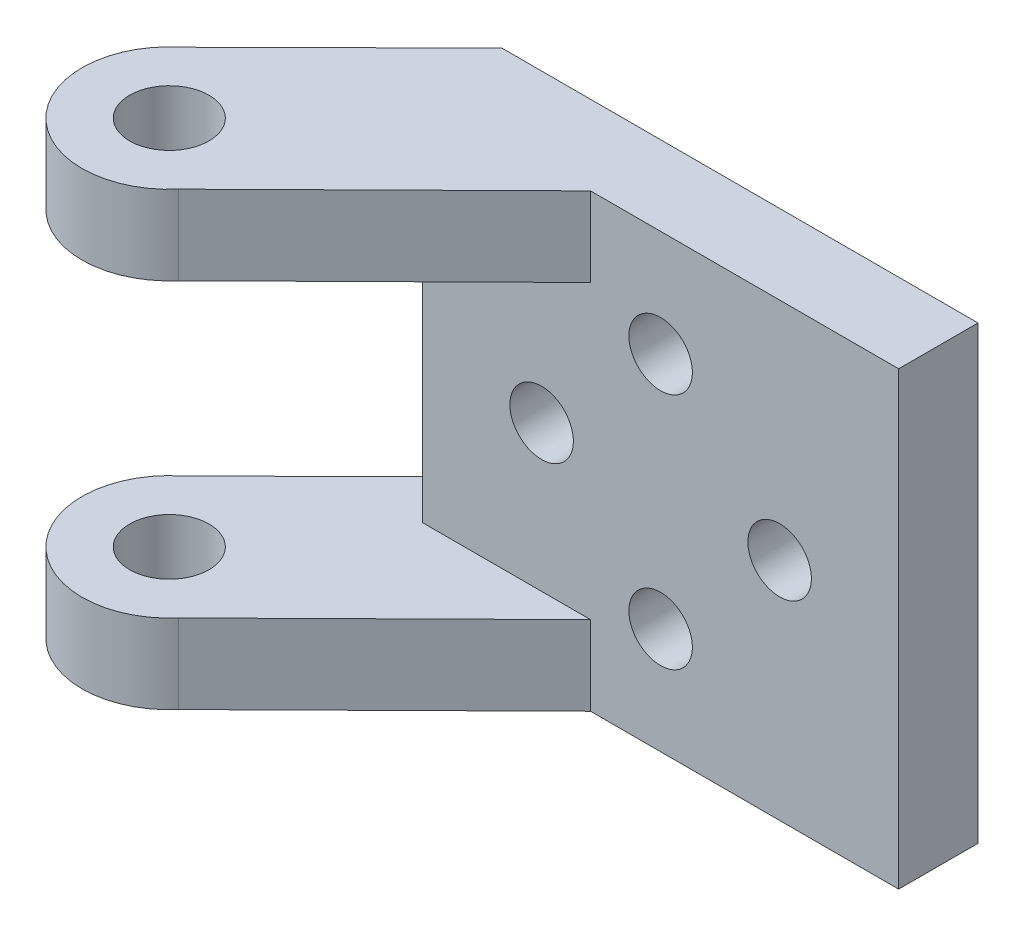
SolidWorks part; units mm, degrees
ref_plane "Front Plane" through (0, 0, 0) normal (0, 0, 1) x (1, 0, 0)
ref_plane "Top Plane" through (0, 0, 0) normal (0, 1, 0) x (1, 0, 0)
ref_plane "Right Plane" through (0, 0, 0) normal (1, 0, 0) x (0, 0, -1)
sketch "Sketch1" plane through (0, 0, 0) normal (0, 1, 0) x (1, 0, 0)
  line L0 (20.0496, 15.0555) -> (-9.9504, 15.0555)
  line L1 (-9.9504, 15.0555) -> (-20.0724, 5.0303)
  line L2 (-12.4366, -2.8246) -> (0.633, 10.0555)
  line L3 (0.633, 10.0555) -> (20.0496, 10.0555)
  line L4 (20.0496, 10.0555) -> (20.0496, 15.0555)
  arc A0 (-20.0724, 5.0303) -> (-12.4366, -2.8246) centre (-16.6118, 0.7555) ccw
  circle A1 centre (-16.6118, 0.7555) radius 2.5
extrude "Boss-Extrude1" add sketch "Sketch1" along normal blind 5
sketch "Sketch2" plane through (0, 0, -15.0555) normal (0, 0, -1) x (-1, 0, 0)
  line L0 (9.9504, 23.4) -> (9.9504, 28.4)
  line L1 (9.9504, 28.4) -> (-20.0496, 28.4)
  line L2 (-20.0496, 28.4) -> (-20.0496, 0)
  line L3 (-20.0496, 0) -> (9.9504, 0)
  line L4 (9.9504, 0) -> (9.9504, 5)
  line L5 (9.9504, 5) -> (9.9504, 23.4)
  line L6 (-20.0496, 0) -> (9.9504, 0) construction
  line L7 (-20.0496, 0) -> (9.9504, 0)
  circle A0 centre (2.4504, 14.2) radius 2
  circle A1 centre (-12.5496, 14.2) radius 2
  circle A2 centre (-5.0496, 21.7) radius 2
  circle A3 centre (-5.0496, 6.7) radius 2
  line M3 (9.9504, 5) -> (-20.0496, 5)
extrude "Boss-Extrude2" add sketch "Sketch2" against normal blind 5 contours A3 L5 L0 L1 L2 A2 A1 A0 M3 region at (5.0496, 16.8849, -15.0555)
extrude "Cut-Extrude1" cut sketch "Sketch2<3>" against normal through all contours A3 M3 region at (5.0496, 4.8792, -15.0555)
sketch "Sketch2<3>" plane through (0, 0, -15.0555) normal (0, 0, -1) x (-1, 0, 0) same geometry as "Sketch2"
sketch "Sketch3" plane through (0, 28.4, 0) normal (0, 1, 0) x (1, 0, 0)
  line L4 (-9.9504, 10.0555) -> (-9.9504, 15.0555)
  line L5 (-9.9504, 15.0555) -> (-20.0724, 5.0303)
  line L6 (-12.4366, -2.8246) -> (0.633, 10.0555)
  line L7 (0.633, 10.0555) -> (-9.9504, 10.0555)
  line L8 (-9.9504, 10.0555) -> (-9.9504, 15.0555)
  line L9 (-9.9504, 15.0555) -> (-20.0724, 5.0303)
  line L10 (-12.4366, -2.8246) -> (0.633, 10.0555)
  line L11 (0.633, 10.0555) -> (-9.9504, 10.0555)
  circle A0 centre (-16.6118, 0.7555) radius 2.5 construction
  arc A1 (-20.0724, 5.0303) -> (-12.4366, -2.8246) centre (-16.6118, 0.7555) ccw
  arc A2 (-20.0724, 5.0303) -> (-12.4366, -2.8246) centre (-16.6118, 0.7555) ccw
  circle A3 centre (-16.6118, 0.7555) radius 2.5
  dimension "D1" = 0
extrude "Boss-Extrude3" add sketch "Sketch3" against normal blind 5
